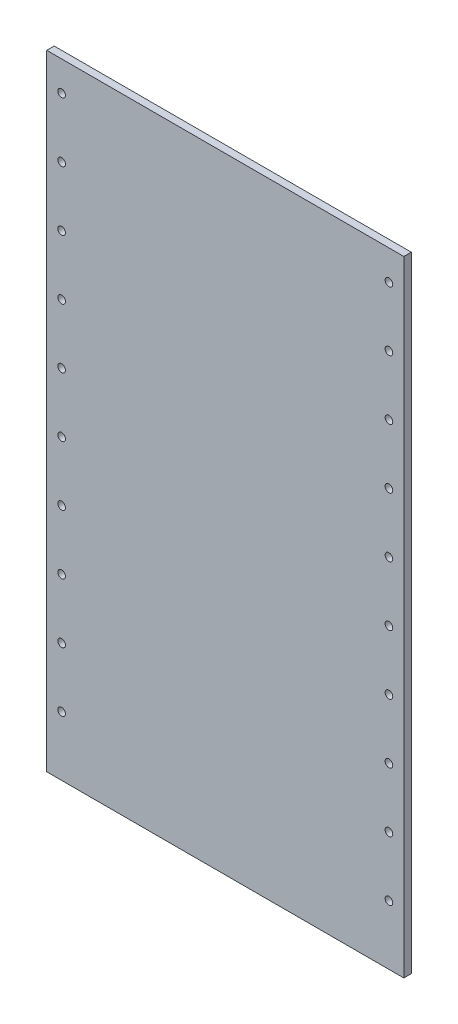
SolidWorks part; units mm, degrees
material "Copper"
ref_plane "Front Plane" through (0, 0, 0) normal (0, 0, 1) x (1, 0, 0)
ref_plane "Top Plane" through (0, 0, 0) normal (0, 1, 0) x (1, 0, 0)
ref_plane "Right Plane" through (0, 0, 0) normal (1, 0, 0) x (0, 0, -1)
sketch "Sketch1" plane through (0, 0, 0) normal (0, 0, 1) x (1, 0, 0)
  line L1 (0, 0) -> (152.4, 0)
  line L2 (0, 0) -> (0, -266.7)
  line L3 (0, -266.7) -> (152.4, -266.7)
  line L4 (152.4, 0) -> (152.4, -266.7)
  circle A0 centre (6.35, -12.7) radius 1.632
  circle A1 centre (146.05, -12.7) radius 1.632
  circle A2 centre (146.05, -38.1) radius 1.632
  circle A3 centre (146.05, -63.5) radius 1.632
  circle A4 centre (146.05, -88.9) radius 1.632
  circle A5 centre (146.05, -114.3) radius 1.632
  circle A6 centre (146.05, -139.7) radius 1.632
  circle A7 centre (146.05, -165.1) radius 1.632
  circle A8 centre (146.05, -190.5) radius 1.632
  circle A9 centre (146.05, -215.9) radius 1.632
  circle A10 centre (146.05, -241.3) radius 1.632
  circle A11 centre (6.35, -38.1) radius 1.6319
  circle A12 centre (6.35, -63.5) radius 1.6319
  circle A13 centre (6.35, -88.9) radius 1.6319
  circle A14 centre (6.35, -114.3) radius 1.6319
  circle A15 centre (6.35, -139.7) radius 1.6319
  circle A16 centre (6.35, -165.1) radius 1.632
  circle A17 centre (6.35, -190.5) radius 1.632
  circle A18 centre (6.35, -215.9) radius 1.632
  circle A19 centre (6.35, -241.3) radius 1.632
  dimension "D3" = 3.2639
  dimension "D1" = 266.7
  dimension "D2" = 152.4
  dimension "D4" = 12.7
  dimension "D5" = 6.35
  dimension "D8" = 6.35
  dimension "D9" = 25.4
  dimension "D6" = 2
  dimension "D7" = 10
extrude "Boss-Extrude1" add sketch "Sketch1" along normal blind 3.175
